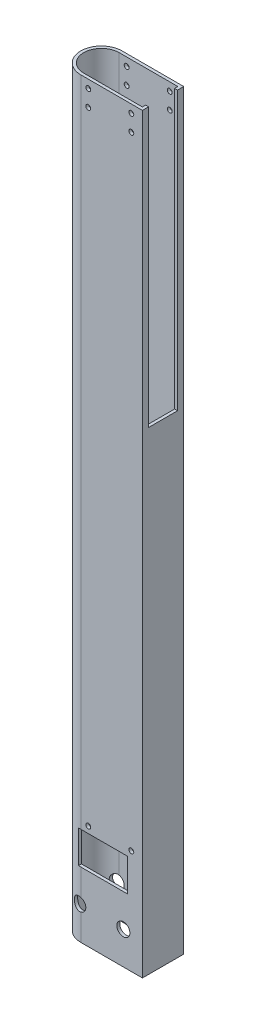
SolidWorks part; units mm, degrees
note: '?' marks a value the reader was unsure of.
ref_plane "Ebene vorne" through (0, 0, 0) normal (0, 0, 1) x (1, 0, 0)
ref_plane "Ebene oben" through (0, 0, 0) normal (0, 1, 0) x (1, 0, 0)
ref_plane "Ebene rechts" through (0, 0, 0) normal (1, 0, 0) x (0, 0, -1)
sketch "Skizze8" plane through (0, 0, 0) normal (0, 0, 1) x (1, 0, 0)
  line L0 (0, 170) -> (0, 630)
sketch "Skizze11" plane through (0, 0, 0) normal (0, 1, 0) x (1, 0, 0)
  line L1 (-12.6, 12.65) -> (25.15, 12.65)
  line L2 (25.15, 12.65) -> (25.15, -12.65)
  line L3 (25.15, -12.65) -> (-12.6, -12.65)
  line L5 (-12.6, 10.85) -> (23.35, 10.85)
  line L6 (23.35, 10.85) -> (23.35, -10.85)
  line L7 (23.35, -10.85) -> (-12.6, -10.85)
  arc A0 (-12.6, 12.65) -> (-12.6, -12.65) centre (-12.6, 0) ccw
  arc A1 (-12.6, 10.85) -> (-12.6, -10.85) centre (-12.6, 0) ccw
sketch "Skizze10"
  line L22 (25.15, 12.65) -> (-12.6, 12.65)
  line L23 (25.15, -12.65) -> (25.15, 12.65)
  line L24 (-12.6, -12.65) -> (25.15, -12.65)
  line L25 (25.15, 12.65) -> (-12.6, 12.65)
  line L26 (25.15, -12.65) -> (25.15, 12.65)
  line L27 (-12.6, -12.65) -> (25.15, -12.65)
  line L31 (23.35, 10.85) -> (-12.6, 10.85)
  line L32 (23.35, -10.85) -> (23.35, 10.85)
  line L33 (-12.6, -10.85) -> (23.35, -10.85)
  line L34 (23.35, 10.85) -> (-12.6, 10.85)
  line L35 (23.35, -10.85) -> (23.35, 10.85)
  line L36 (-12.6, -10.85) -> (23.35, -10.85)
  arc A6 (-12.6, 12.65) -> (-12.6, -12.65) centre (-12.6, 0) ccw
  arc A7 (-12.6, 12.65) -> (-12.6, -12.65) centre (-12.6, 0) ccw
  arc A9 (-12.6, 10.85) -> (-12.6, -10.85) centre (-12.6, 0) ccw
  arc A10 (-12.6, 10.85) -> (-12.6, -10.85) centre (-12.6, 0) ccw
  dimension "D1" = 0
  dimension "D2" = 0
extrude "Aufsatz-Linear austragen2" add sketch "Skizze10" along normal up to vertex (630 mm away) from vertex at 170
sketch "Skizze14" plane through (0, 0, 0) normal (0, 0, 1) x (1, 0, 0)
  circle A0 centre (13.5, 190) radius 4
  circle A1 centre (-13.5, 190) radius 4
sketch "Skizze15" plane through (0, 0, 0) normal (0, 0, 1) x (1, 0, 0)
  circle A0 centre (-13.5, 190) radius 4
  circle A1 centre (13.5, 190) radius 4
extrude "Schnitt-Linear austragen1" cut sketch "Skizze15" against normal up to surface and the other way up to surface up to face at (6.275, 400, -12.65) other way up to face at (6.275, 400, 12.65)
sketch "Skizze16" plane through (0, 0, 0) normal (0, 0, 1) x (1, 0, 0)
  line L1 (-14, 210) -> (16, 210)
  line L2 (-14, 210) -> (-14, 230)
  line L3 (-14, 230) -> (16, 230)
  line L4 (16, 210) -> (16, 230)
  line L5 (-14, 210) -> (16, 230) construction
  line L6 (-14, 230) -> (16, 210) construction
  point P0 (1, 220)
sketch "Skizze17" plane through (0, 0, 0) normal (0, 0, 1) x (1, 0, 0)
  line L1 (-14, 210) -> (16, 210)
  line L2 (-14, 210) -> (-14, 230)
  line L3 (-14, 230) -> (16, 230)
  line L4 (16, 210) -> (16, 230)
  line L5 (-14, 210) -> (16, 230) construction
  line L6 (-14, 230) -> (16, 210) construction
  point P0 (1, 220)
extrude "Schnitt-Linear austragen2" cut sketch "Skizze17" along normal up to surface (12.65 mm away) up to face at (9.5, 190, 12.65)
sketch "Skizze18" plane through (0, 0, 0) normal (1, 0, 0) x (0, 0, -1)
  line L1 (8.85, 630) -> (-8.85, 630)
  line L2 (0, 630) -> (0, 460)
  line L3 (8.85, 460) -> (-8.85, 460)
  line L4 (-8.85, 630) -> (-8.85, 460)
  line L5 (8.85, 630) -> (8.85, 460)
sketch "Skizze19" plane through (0, 0, 0) normal (1, 0, 0) x (0, 0, -1)
  line L1 (8.85, 630) -> (-8.85, 630)
  line L2 (8.85, 630) -> (8.85, 460)
  line L3 (8.85, 460) -> (-8.85, 460)
  line L4 (-8.85, 630) -> (-8.85, 460)
extrude "Schnitt-Linear austragen3" cut sketch "Skizze19" along normal up to surface (25.15 mm away) up to face at (25.15, 400, 0)
sketch "Skizze20" plane through (0, 0, 0) normal (0, 0, 1) x (1, 0, 0)
  circle A0 centre (0, 670) radius 3.25
  circle A1 centre (70, 670) radius 3.25
sketch "Skizze21" plane through (0, 0, 0) normal (0, 0, 1) x (1, 0, 0)
  circle A0 centre (0, 670) radius 4
extrude "Schnitt-Linear austragen4" [suppressed] cut sketch "Skizze21" against normal through all both and the other way through all
sketch "HolesPlates" plane through (0, 0, 0) normal (0, 0, 1) x (1, 0, 0)
  line L0 (0, 234) -> (28.7572, 234) construction
  line L3 (0, 615) -> (28.7572, 615) construction
  circle A0 centre (18.35, 234) radius 1.25
  circle A1 centre (-8, 234) radius 1.25
  circle A2 centre (18.35, 615) radius 1.25
  circle A3 centre (-8, 615) radius 1.25
sketch "Holes" plane through (0, 0, 0) normal (0, 0, 1) x (1, 0, 0)
  circle A0 centre (18.35, 615) radius 1.5
  circle A1 centre (-8, 615) radius 1.5
  circle A2 centre (18.35, 234) radius 1.5
  circle A3 centre (-8, 234) radius 1.5
extrude "Schnitt-Linear austragen5" cut sketch "Holes" against normal through all both and the other way through all
sketch "Skizze22" plane through (0, 0, 0) normal (0, 0, 1) x (1, 0, 0)
  line L1 (-12.6, 630) -> (23.35, 630)
  line L2 (-12.6, 630) -> (-12.6, 620)
  line L3 (-12.6, 620) -> (23.35, 620)
  line L4 (23.35, 630) -> (23.35, 620)
  line L5 (-12.6, 625) -> (23.35, 625) construction
  circle A0 centre (18.35, 625) radius 1.25
  circle A1 centre (-8, 625) radius 1.25
sketch "Skizze23" plane through (0, 0, 0) normal (0, 0, 1) x (1, 0, 0)
  circle A0 centre (-8, 625) radius 1.5
  circle A1 centre (18.35, 625) radius 1.5
extrude "Schnitt-Linear austragen7" cut sketch "Skizze23" along normal through all both and the other way through all
ref_axis "Achse1" through (18.35, 615, 10.85) along (0, 0, 1)?
ref_axis "Achse2" through (18.35, 625, 12.65) along (0, 0, -1)?
